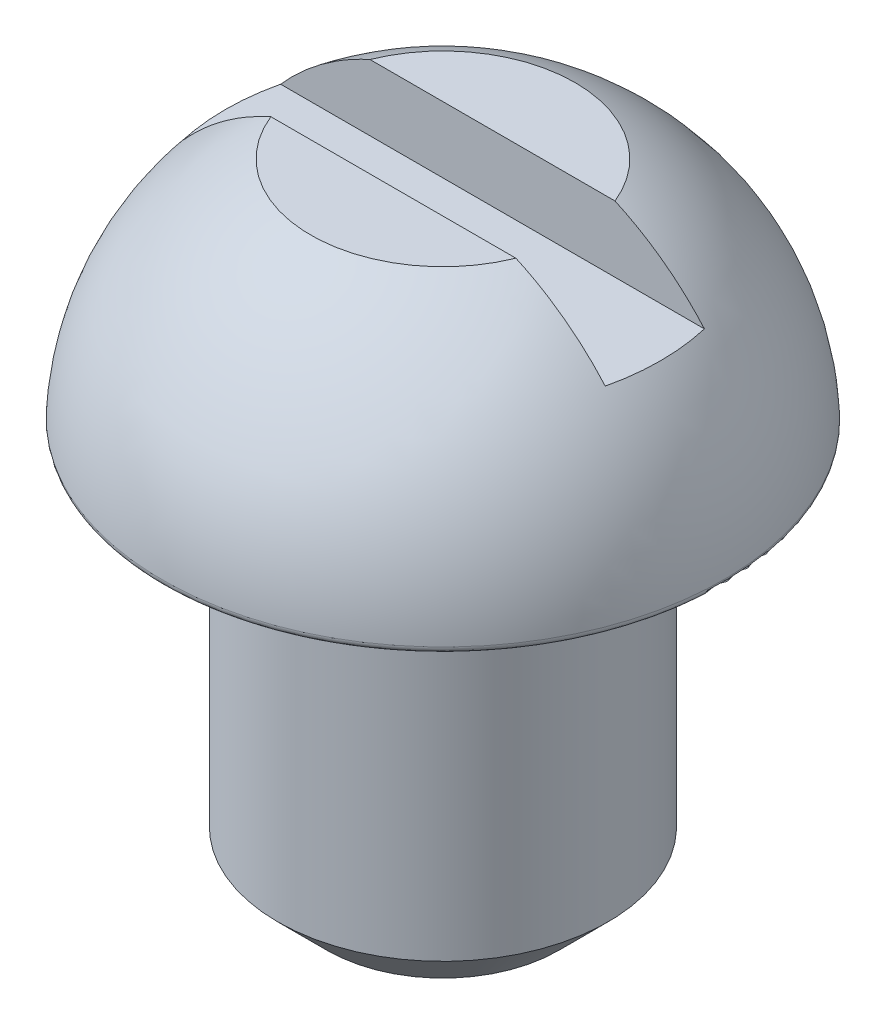
SolidWorks part; units mm, degrees
ref_plane "Спереди" through (0, 0, 0) normal (0, 0, 1) x (1, 0, 0)
ref_plane "Сверху" through (0, 0, 0) normal (0, 1, 0) x (1, 0, 0)
ref_plane "Справа" through (0, 0, 0) normal (1, 0, 0) x (0, 0, -1)
sketch "Эскиз1" plane through (0, 0, 0) normal (0, 0, 1) x (1, 0, 0)
  line L0 (4.25, 6) -> (2.5, 6)
  line L1 (0, 0) -> (0, 9.5)
  line L2 (2.5, 6) -> (2.5, 0.75)
  line L3 (2.5, 0.75) -> (1.75, 0)
  line L4 (1.75, 0) -> (0, 0)
  line L5 (0, 9.5) -> (2, 9.5)
  arc A0 (2, 9.5) -> (4.25, 6) centre (0.2512, 5.9025) cw
  point P9 (0, 0)
  dimension "D2" = 2
  dimension "D3" = 4
  dimension "D1" = 9.5
  dimension "D4" = 0.75
  dimension "D5" = 3.5
  dimension "D6" = 4.25
  dimension "D7" = 45
  dimension "D9" = 2.5
revolve "Повернуть1" add sketch "Эскиз1" angle 360 about L1
fillet "Скругление1" radius 0.1 1 edges at (0, 6, -4.25)
sketch "Эскиз3" plane through (0, 9.5, 0) normal (0, 1, 0) x (-1, 0, 0)
  line L1 (4, -0.75) -> (-4, -0.75)
  line L2 (4, -0.75) -> (4, 0.75)
  line L3 (4, 0.75) -> (-4, 0.75)
  line L4 (-4, -0.75) -> (-4, 0.75)
  dimension "D1" = 1.5
  dimension "D2" = 0.75
  dimension "D3" = 8
  dimension "D4" = 4
extrude "Вырез-Вытянуть2" cut sketch "Эскиз3" against normal blind 1
ref_axis "Ось1" through (0, -104.1565, 0) along (0, 1, 0)
